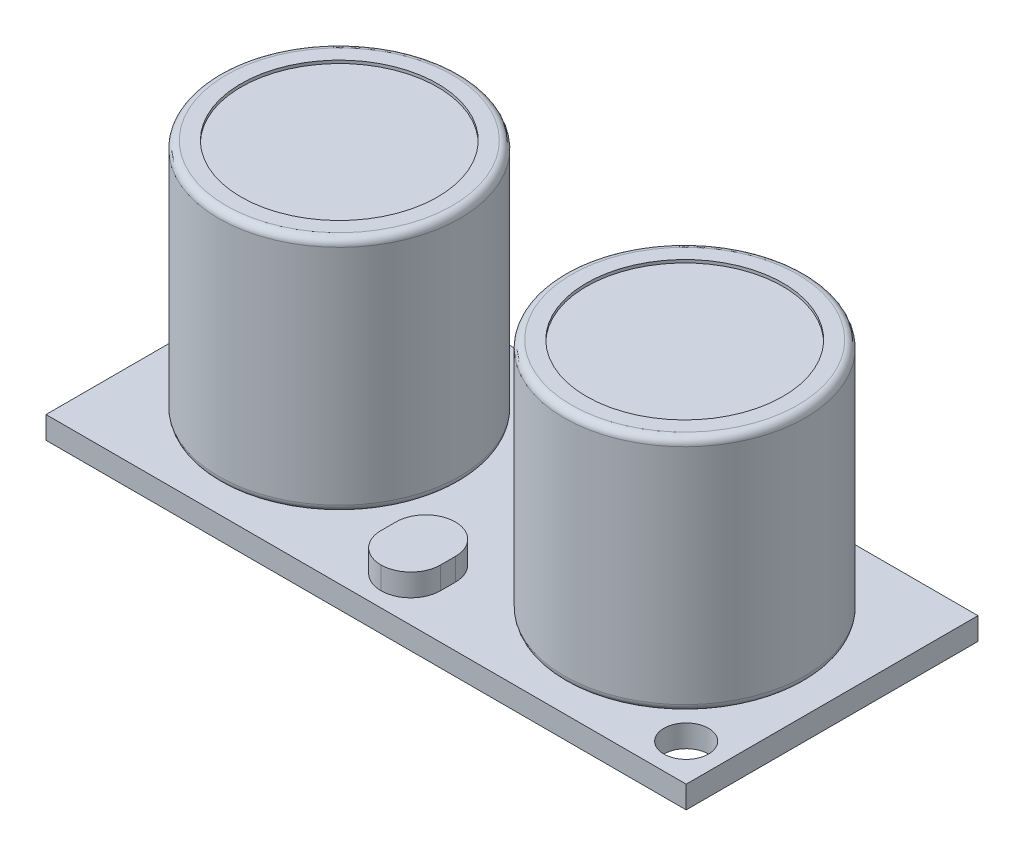
SolidWorks part; units mm, degrees
ref_plane "Front Plane" through (0, 0, 0) normal (0, 0, 1) x (1, 0, 0)
ref_plane "Top Plane" through (0, 0, 0) normal (0, 1, 0) x (1, 0, 0)
ref_plane "Right Plane" through (0, 0, 0) normal (1, 0, 0) x (0, 0, -1)
sketch "Sketch1" plane through (0, 0, 0) normal (0, 1, 0) x (1, 0, 0)
  circle A0 centre (0, 0) radius 8.1
  circle A1 centre (23.2, 0) radius 8.1
  dimension "D1" = 16.2
  dimension "D2" = 16.2
extrude "Extrude1" add sketch "Sketch1" along normal blind 16
sketch "Sketch2" plane through (0, 16, 0) normal (0, 1, 0) x (-1, 0, 0)
  circle A0 centre (-23.2, 0) radius 6.6
  circle A1 centre (0, 0) radius 6.6
  dimension "D1" = 13.2
  dimension "D2" = 13.2
fillet "Fillet1" radius 0.5 2 edges at (0, 0, 8.1) (0, 16, 8.1)
extrude "Cut-Extrude2" cut sketch "Sketch2" against normal blind 0.2
fillet "Fillet2" radius 0.5 2 edges at (23.2, 0, 8.1) (23.2, 16, 8.1)
sketch "Sketch3" plane through (0, 0, 0) normal (0, -1, 0) x (1, 0, 0)
  line L1 (33.1, 9.8) -> (33.1, -9.8)
  line L4 (33.1, -9.8) -> (-9.9, -9.8)
  line L5 (-9.9, 9.8) -> (-9.9, -9.8)
  line L6 (33.1, 9.8) -> (-9.9, 9.8)
  circle A0 centre (-7.4, -7.3) radius 1.5
  circle A1 centre (30.6, 7.3) radius 1.5
  dimension "D1" = 2.5
  dimension "D5" = 3
  dimension "D8" = 3
  dimension "D2" = 19.6
  dimension "D3" = 43
  dimension "D4" = 2.5
  dimension "D6" = 2.5
  dimension "D7" = 2.5
extrude "Extrude2" add sketch "Sketch3" along normal blind 1.5
sketch "Sketch4" plane through (0, 0, 0) normal (0, 1, 0) x (-1, 0, 0)
  line L0 (-11.6, 9.8) -> (-11.6, -9.8)
  line L1 (-33.1, 9.8) -> (9.9, 9.8) construction
  line L2 (9.9, -9.8) -> (-33.1, -9.8) construction
  line L3 (-9.6, 3.8) -> (-9.6, 8.8)
  line L4 (-9.6, 3.8) -> (-13.6, 3.8)
  line L5 (-11.6, 3.8) -> (-11.6, 8.8)
  line L6 (-9.6, 8.8) -> (-13.6, 8.8)
  line L7 (-13.6, 3.8) -> (-13.6, 8.8)
  dimension "D1" = 5
  dimension "D2" = 4
  dimension "D3" = 1
extrude "Extrude3" add sketch "Sketch4" along normal blind 1.5 contours L3 L6 L0 L4 | L7 L4 L0 L6
fillet "Fillet3" radius 2 4 edges at (9.6, 0.75, 3.8) (13.6, 0.75, 3.8) (9.6, 0.75, 8.8) (13.6, 0.75, 8.8)
